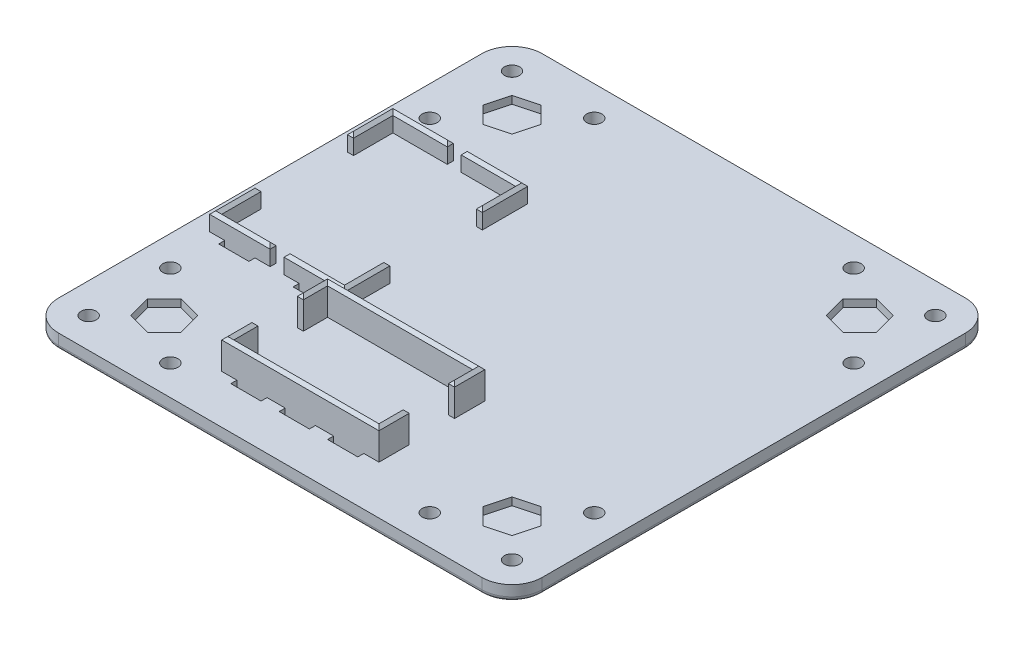
SolidWorks part; units mm, degrees
ref_plane "Front Plane" through (0, 0, 0) normal (0, 0, 1) x (1, 0, 0)
ref_plane "Top Plane" through (0, 0, 0) normal (0, 1, 0) x (1, 0, 0)
ref_plane "Right Plane" through (0, 0, 0) normal (1, 0, 0) x (0, 0, -1)
sketch "Sketch1" plane through (0, 0, 0) normal (0, 1, 0) x (1, 0, 0)
  line L1 (0, 0) -> (203.2, 0)
  line L2 (0, 0) -> (0, 203.2)
  line L3 (0, 203.2) -> (203.2, 203.2)
  line L4 (203.2, 0) -> (203.2, 203.2)
  dimension "D1" = 203.2
  dimension "D2" = 203.2
extrude "Boss-Extrude1" add sketch "Sketch1" along normal blind 6.35
fillet "Fillet1" radius 12.7 4 edges at (0, 3.175, -203.2) (0, 3.175, 0) (203.2, 3.175, 0) (203.2, 3.175, -203.2)
sketch "Sketch2" plane through (0, 0, 0) normal (0, -1, 0) x (1, 0, 0)
  circle A0 centre (12.7, -12.7) radius 3.175
  circle A1 centre (190.5, -12.7) radius 3.175
  circle A2 centre (190.5, -190.5) radius 3.175
  circle A3 centre (12.7, -190.5) radius 3.175
  arc A4 (190.5, -203.2) -> (203.2, -190.5) centre (190.5, -190.5) ccw construction
  arc A5 (12.7, 0) -> (0, -12.7) centre (12.7, -12.7) ccw construction
  dimension "D1" = 6.35
extrude "Cut-Extrude1" cut sketch "Sketch2" against normal through all
sketch "Sketch22" plane through (0, 6.35, 0) normal (0, 1, 0) x (1, 0, 0)
  line L17 (190.5, 203.2) -> (12.7, 203.2) construction
  line L18 (203.2, 12.7) -> (203.2, 190.5) construction
  line L21 (181.6542, 181.6542) -> (172.0521, 184.2271)
  line L22 (172.0521, 184.2271) -> (165.0229, 177.1979)
  line L23 (165.0229, 177.1979) -> (167.5958, 167.5958)
  line L24 (167.5958, 167.5958) -> (177.1979, 165.0229)
  line L25 (177.1979, 165.0229) -> (184.2271, 172.0521)
  line L26 (184.2271, 172.0521) -> (181.6542, 181.6542)
  line L27 (174.625, 174.625) -> (190.5, 190.5) construction
  line L28 (101.6, 203.2) -> (101.6, 0) construction
  line L29 (12.7, 0) -> (190.5, 0) construction
  line L30 (203.2, 101.6) -> (0, 101.6) construction
  line L31 (0, 190.5) -> (0, 12.7) construction
  line L32 (28.575, 174.625) -> (12.7, 190.5) construction
  line L33 (18.9729, 172.0521) -> (21.5458, 181.6542)
  line L34 (26.0021, 165.0229) -> (18.9729, 172.0521)
  line L35 (35.6042, 167.5958) -> (26.0021, 165.0229)
  line L36 (38.1771, 177.1979) -> (35.6042, 167.5958)
  line L37 (31.1479, 184.2271) -> (38.1771, 177.1979)
  line L38 (21.5458, 181.6542) -> (31.1479, 184.2271)
  line L39 (174.625, 28.575) -> (190.5, 12.7) construction
  line L40 (184.2271, 31.1479) -> (181.6542, 21.5458)
  line L41 (177.1979, 38.1771) -> (184.2271, 31.1479)
  line L42 (167.5958, 35.6042) -> (177.1979, 38.1771)
  line L43 (165.0229, 26.0021) -> (167.5958, 35.6042)
  line L44 (172.0521, 18.9729) -> (165.0229, 26.0021)
  line L45 (181.6542, 21.5458) -> (172.0521, 18.9729)
  line L46 (28.575, 28.575) -> (12.7, 12.7) construction
  line L47 (21.5458, 21.5458) -> (31.1479, 18.9729)
  line L48 (31.1479, 18.9729) -> (38.1771, 26.0021)
  line L49 (38.1771, 26.0021) -> (35.6042, 35.6042)
  line L50 (35.6042, 35.6042) -> (26.0021, 38.1771)
  line L51 (26.0021, 38.1771) -> (18.9729, 31.1479)
  line L52 (18.9729, 31.1479) -> (21.5458, 21.5458)
  circle A0 centre (174.625, 174.625) radius 8.609 construction
  circle A1 centre (28.575, 174.625) radius 8.609 construction
  circle A2 centre (174.625, 28.575) radius 8.609 construction
  circle A3 centre (28.575, 28.575) radius 8.609 construction
  dimension "D5" = 17.218
  dimension "D3" = 28.575
  dimension "D4" = 28.575
extrude "Cut-Extrude2" cut sketch "Sketch22" against normal blind 3.175
sketch "Sketch23" plane through (0, 6.35, 0) normal (0, 1, 0) x (1, 0, 0)
  line L1 (64.262, 145.542) -> (38.862, 145.542)
  line L2 (64.262, 145.542) -> (64.262, 126.492)
  line L3 (64.262, 68.58) -> (38.862, 68.58)
  line L4 (7.62, 145.542) -> (7.62, 126.492)
  line L5 (7.62, 145.542) -> (7.62, 203.2) construction
  line L6 (190.5, 203.2) -> (12.7, 203.2) construction
  line L7 (7.62, 68.58) -> (7.62, 0) construction
  line L8 (12.7, 0) -> (190.5, 0) construction
  line L9 (33.02, 145.542) -> (33.02, 143.002)
  line L10 (61.722, 143.002) -> (38.862, 143.002)
  line L11 (61.722, 143.002) -> (61.722, 126.492)
  line L12 (61.722, 71.12) -> (38.862, 71.12)
  line L13 (10.16, 143.002) -> (10.16, 126.492)
  line L14 (38.862, 145.542) -> (38.862, 143.002)
  line L15 (64.262, 126.492) -> (61.722, 126.492)
  line L16 (64.262, 87.63) -> (61.722, 87.63)
  line L17 (10.16, 126.492) -> (7.62, 126.492)
  line L18 (10.16, 87.63) -> (7.62, 87.63)
  line L19 (33.02, 71.12) -> (33.02, 68.58)
  line L20 (38.862, 71.12) -> (38.862, 68.58)
  line L21 (33.02, 145.542) -> (7.62, 145.542)
  line L22 (33.02, 143.002) -> (10.16, 143.002)
  line L23 (64.262, 87.63) -> (64.262, 68.58)
  line L24 (61.722, 87.63) -> (61.722, 71.12)
  line L25 (33.02, 71.12) -> (10.16, 71.12)
  line L26 (33.02, 68.58) -> (7.62, 68.58)
  line L27 (10.16, 87.63) -> (10.16, 71.12)
  line L28 (7.62, 87.63) -> (7.62, 68.58)
  line L29 (0, 190.5) -> (0, 12.7) construction
  point P32 (33.02, 144.272)
  dimension "D2" = 71.882
  dimension "D3" = 51.562
  dimension "D4" = 2.54
  dimension "D5" = 2.54
  dimension "D6" = 2.54
  dimension "D7" = 2.54
  dimension "D8" = 19.05
  dimension "D9" = 19.05
  dimension "D10" = 25.4
  dimension "D11" = 25.4
  dimension "D12" = 19.05
  dimension "D13" = 19.05
  dimension "D14" = 25.4
  dimension "D15" = 25.4
  dimension "D17" = 7.62
  dimension "D18" = 134.62
extrude "Boss-Extrude2" add sketch "Sketch23" along normal blind 7.62
chamfer "Chamfer1" distance 1.27 angle 45 24 edges at (8.89, 13.97, -87.63) (10.16, 13.97, -79.375) (21.59, 13.97, -71.12) (33.02, 13.97, -69.85) (20.32, 13.97, -68.58) (7.62, 13.97, -78.105) (51.562, 13.97, -68.58) (38.862, 13.97, -69.85) (50.292, 13.97, -71.12) (61.722, 13.97, -79.375) (62.992, 13.97, -87.63) (64.262, 13.97, -78.105) (62.992, 13.97, -126.492) (61.722, 13.97, -134.747) (50.292, 13.97, -143.002) (38.862, 13.97, -144.272) (51.562, 13.97, -145.542) (64.262, 13.97, -136.017) (33.02, 13.97, -144.272) (21.59, 13.97, -143.002) (10.16, 13.97, -134.747) (8.89, 13.97, -126.492) (7.62, 13.97, -136.017) (20.32, 13.97, -145.542)
sketch "Sketch24" plane through (0, 6.35, 0) normal (0, 1, 0) x (1, 0, 0)
  line L0 (12.7, 0) -> (190.5, 0) construction
  line L1 (124.46, 62.23) -> (63.5, 62.23)
  line L2 (124.46, 62.23) -> (124.46, 52.07)
  line L3 (124.46, 22.86) -> (63.5, 22.86)
  line L4 (63.5, 62.23) -> (63.5, 52.07)
  line L5 (0, 190.5) -> (0, 12.7) construction
  line L6 (127, 64.77) -> (60.96, 64.77)
  line L7 (127, 64.77) -> (127, 52.07)
  line L8 (127, 20.32) -> (60.96, 20.32)
  line L9 (60.96, 64.77) -> (60.96, 52.07)
  line L10 (60.96, 52.07) -> (63.5, 52.07)
  line L11 (60.96, 33.02) -> (63.5, 33.02)
  line L12 (60.96, 33.02) -> (60.96, 20.32)
  line L13 (63.5, 33.02) -> (63.5, 22.86)
  line L14 (124.46, 52.07) -> (127, 52.07)
  line L15 (124.46, 33.02) -> (127, 33.02)
  line L16 (124.46, 33.02) -> (124.46, 22.86)
  line L17 (127, 33.02) -> (127, 20.32)
  dimension "D1" = 39.37
  dimension "D2" = 60.96
  dimension "D3" = 22.86
  dimension "D4" = 2.54
  dimension "D5" = 2.54
  dimension "D6" = 2.54
  dimension "D7" = 2.54
  dimension "D8" = 63.5
  dimension "D9" = 12.7
  dimension "D10" = 12.7
extrude "Boss-Extrude3" add sketch "Sketch24" along normal blind 12.7
chamfer "Chamfer2" distance 1.27 angle 45 16 edges at (93.98, 19.05, -62.23) (63.5, 19.05, -57.15) (62.23, 19.05, -52.07) (60.96, 19.05, -58.42) (93.98, 19.05, -64.77) (127, 19.05, -58.42) (93.98, 19.05, -20.32) (60.96, 19.05, -26.67) (62.23, 19.05, -33.02) (63.5, 19.05, -27.94) (93.98, 19.05, -22.86) (124.46, 19.05, -57.15) (125.73, 19.05, -52.07) (124.46, 19.05, -27.94) (125.73, 19.05, -33.02) (127, 19.05, -26.67)
fillet "Fillet2" radius 1.905 12 edges at (3.7197, 0, -3.7197) (101.6, 0, 0) (199.4803, 0, -3.7197) (203.2, 0, -101.6) (199.4803, 0, -199.4803) (101.6, 0, -203.2) (3.7197, 0, -199.4803) (0, 0, -101.6) (12.7, 0, -15.875) (190.5, 0, -15.875) (190.5, 0, -193.675) (12.7, 0, -193.675)
sketch "Sketch27" plane through (0, 6.35, 0) normal (0, 1, 0) x (1, 0, 0)
  line L0 (38.862, 143.002) -> (61.722, 143.002) construction
  line L1 (85.852, 143.002) -> (137.414, 143.002)
  line L2 (85.852, 143.002) -> (85.852, 129.032)
  line L3 (85.852, 71.12) -> (137.414, 71.12)
  line L4 (137.414, 143.002) -> (137.414, 129.032)
  line L5 (83.312, 145.542) -> (83.312, 129.032)
  line L6 (83.312, 68.58) -> (139.954, 68.58)
  line L7 (139.954, 145.542) -> (139.954, 129.032)
  line L8 (83.312, 145.542) -> (139.954, 145.542)
  line L9 (83.312, 129.032) -> (85.852, 129.032)
  line L10 (83.312, 90.17) -> (85.852, 90.17)
  line L11 (137.414, 90.17) -> (139.954, 90.17)
  line L12 (139.954, 129.032) -> (137.414, 129.032)
  line L13 (83.312, 90.17) -> (83.312, 68.58)
  line L14 (83.312, 145.542) -> (83.312, 68.58) construction
  line L15 (85.852, 90.17) -> (85.852, 71.12)
  line L16 (85.852, 143.002) -> (85.852, 71.12) construction
  line L17 (137.414, 90.17) -> (137.414, 71.12)
  line L18 (137.414, 143.002) -> (137.414, 71.12) construction
  line L19 (139.954, 90.17) -> (139.954, 68.58)
  line L20 (139.954, 145.542) -> (139.954, 68.58) construction
  line L21 (64.262, 68.58) -> (64.262, 87.63) construction
  dimension "D1" = 71.882
  dimension "D2" = 51.562
  dimension "D4" = 19.05
  dimension "D3" = 2.54
sketch "Sketch28" plane through (0, 6.35, 0) normal (0, 1, 0) x (1, 0, 0)
  line L0 (190.5, 203.2) -> (12.7, 203.2) construction
  line L1 (203.2, 12.7) -> (203.2, 190.5) construction
  line L2 (12.7, 0) -> (190.5, 0) construction
  line L4 (0, 190.5) -> (0, 12.7) construction
  circle A0 centre (47.117, 190.627) radius 3.175
  circle A1 centre (156.083, 190.627) radius 3.175
  circle A2 centre (190.627, 156.083) radius 3.175
  circle A3 centre (190.627, 47.117) radius 3.175
  circle A4 centre (156.083, 12.573) radius 3.175
  circle A5 centre (47.117, 12.573) radius 3.175
  circle A6 centre (12.573, 156.083) radius 3.175
  circle A7 centre (12.573, 47.117) radius 3.175
  dimension "D4" = 6.35
  dimension "D1" = 12.573
  dimension "D2" = 12.573
  dimension "D3" = 12.573
  dimension "D5" = 12.573
  dimension "D6" = 47.117
  dimension "D7" = 47.117
  dimension "D8" = 47.117
  dimension "D9" = 47.117
extrude "Cut-Extrude3" cut sketch "Sketch28" against normal through all
sketch "Sketch29" plane through (0, 6.35, 0) normal (0, 1, 0) x (1, 0, 0)
  line L0 (33.02, 145.542) -> (7.62, 145.542) construction
  line L1 (13.97, 145.542) -> (26.67, 145.542)
  line L2 (13.97, 145.542) -> (13.97, 148.082)
  line L3 (13.97, 148.082) -> (26.67, 148.082)
  line L4 (26.67, 145.542) -> (26.67, 148.082)
  line L5 (64.262, 145.542) -> (38.862, 145.542) construction
  line L6 (45.212, 145.542) -> (57.912, 145.542)
  line L7 (45.212, 145.542) -> (45.212, 148.082)
  line L8 (45.212, 148.082) -> (57.912, 148.082)
  line L9 (57.912, 145.542) -> (57.912, 148.082)
  line L10 (127, 64.77) -> (60.96, 64.77) construction
  line L11 (67.31, 64.77) -> (80.01, 64.77)
  line L12 (67.31, 64.77) -> (67.31, 67.31)
  line L13 (67.31, 67.31) -> (80.01, 67.31)
  line L14 (80.01, 64.77) -> (80.01, 67.31)
  line L15 (60.96, 20.32) -> (127, 20.32) construction
  line L16 (107.95, 64.77) -> (120.65, 64.77)
  line L17 (107.95, 64.77) -> (107.95, 67.31)
  line L18 (107.95, 67.31) -> (120.65, 67.31)
  line L19 (120.65, 64.77) -> (120.65, 67.31)
  line L20 (67.31, 20.32) -> (80.01, 20.32)
  line L21 (67.31, 20.32) -> (67.31, 17.78)
  line L22 (67.31, 17.78) -> (80.01, 17.78)
  line L23 (80.01, 20.32) -> (80.01, 17.78)
  line L25 (107.95, 20.32) -> (120.65, 20.32)
  line L26 (107.95, 20.32) -> (107.95, 17.78)
  line L27 (107.95, 17.78) -> (120.65, 17.78)
  line L28 (120.65, 20.32) -> (120.65, 17.78)
  line L33 (38.862, 68.58) -> (64.262, 68.58) construction
  line L34 (45.212, 68.58) -> (57.912, 68.58)
  line L35 (45.212, 68.58) -> (45.212, 66.04)
  line L36 (45.212, 66.04) -> (57.912, 66.04)
  line L37 (57.912, 68.58) -> (57.912, 66.04)
  line L38 (33.02, 71.12) -> (10.16, 71.12) construction
  line L40 (33.02, 145.542) -> (33.02, 143.002) construction
  line L41 (38.862, 143.002) -> (38.862, 145.542) construction
  line L42 (38.862, 71.12) -> (38.862, 68.58) construction
  line L44 (7.62, 68.58) -> (33.02, 68.58) construction
  line L45 (13.97, 68.58) -> (26.67, 68.58)
  line L46 (13.97, 68.58) -> (13.97, 66.04)
  line L47 (13.97, 66.04) -> (26.67, 66.04)
  line L48 (26.67, 68.58) -> (26.67, 66.04)
  line L49 (33.02, 68.58) -> (33.02, 71.12) construction
  line L50 (60.96, 64.77) -> (60.96, 52.07) construction
  line L51 (60.96, 33.02) -> (60.96, 20.32) construction
  line L52 (127, 20.32) -> (127, 33.02) construction
  line L53 (127, 64.77) -> (127, 52.07) construction
  line L54 (60.96, 64.77) -> (127, 64.77) construction
  line L55 (87.63, 64.77) -> (100.33, 64.77)
  line L56 (87.63, 64.77) -> (87.63, 67.31)
  line L57 (87.63, 67.31) -> (100.33, 67.31)
  line L58 (100.33, 64.77) -> (100.33, 67.31)
  line L59 (127, 20.32) -> (60.96, 20.32) construction
  line L60 (100.33, 20.32) -> (87.63, 20.32)
  line L61 (100.33, 20.32) -> (100.33, 17.78)
  line L62 (100.33, 17.78) -> (87.63, 17.78)
  line L63 (87.63, 20.32) -> (87.63, 17.78)
  line L64 (63.5, 62.23) -> (124.46, 62.23) construction
  line L65 (124.46, 22.86) -> (63.5, 22.86) construction
  point P47 (21.59, 71.12)
  point P75 (93.98, 67.31)
  point P78 (93.98, 62.23)
  point P79 (93.98, 17.78)
  point P82 (93.98, 22.86)
  dimension "D1" = 12.7
  dimension "D2" = 2.54
  dimension "D3" = 6.35
  dimension "D4" = 6.35
  dimension "D5" = 6.35
  dimension "D6" = 6.35
  dimension "D7" = 6.35
  dimension "D8" = 6.35
  dimension "D9" = 6.35
  dimension "D10" = 6.35
  dimension "D11" = 2.54
extrude "Cut-Extrude4" cut sketch "Sketch29" against normal through all
